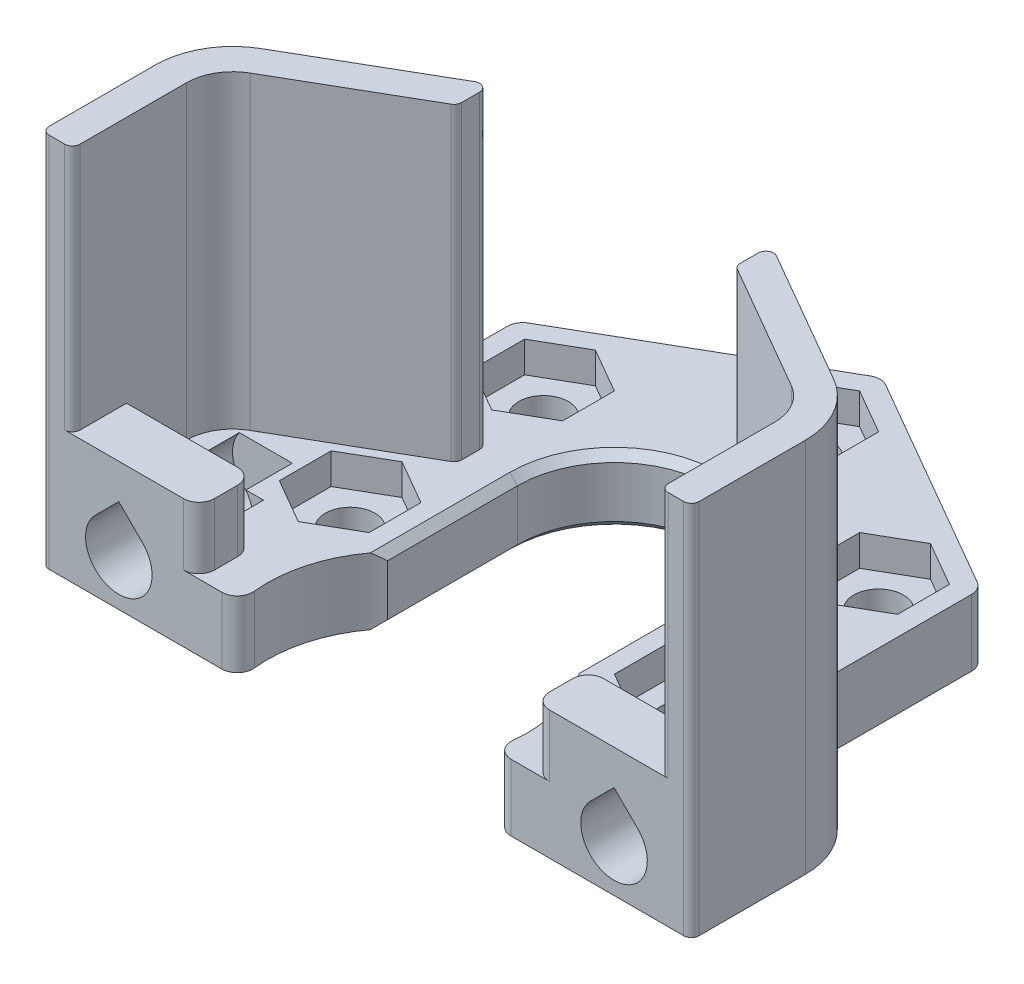
SolidWorks part; units mm, degrees
ref_plane "Front Plane" through (0, 0, 0) normal (0, 0, 1) x (1, 0, 0)
ref_plane "Top Plane" through (0, 0, 0) normal (0, 1, 0) x (1, 0, 0)
ref_plane "Right Plane" through (0, 0, 0) normal (1, 0, 0) x (0, 0, -1)
sketch "Sketch1" plane through (0, 0, 0) normal (0, 1, 0) x (1, 0, 0)
  line L0 (0, 0) -> (0, -54.0828) construction
  line L1 (0, 17.3205) -> (-15, 8.6603)
  line L2 (-15, 8.6603) -> (-15, -8.6603)
  line L3 (-15, -8.6603) -> (-6.25, -13.7121)
  line L4 (6.25, -13.7121) -> (15, -8.6603)
  line L5 (15, -8.6603) -> (15, 8.6603)
  line L6 (15, 8.6603) -> (0, 17.3205)
  line L7 (0, -54.6431) -> (0, 54.6431) construction
  line L8 (6.25, 0) -> (6.25, -13.7121)
  line L9 (-6.25, 0) -> (-6.25, -13.7121)
  line L11 (0, 12.5) -> (-10.8253, 6.25) construction
  line L12 (-10.8253, 6.25) -> (-10.8253, -6.25) construction
  line L13 (-10.8253, -6.25) -> (0, -12.5) construction
  line L14 (0, -12.5) -> (10.8253, -6.25) construction
  line L15 (10.8253, -6.25) -> (10.8253, 6.25) construction
  line L16 (10.8253, 6.25) -> (0, 12.5) construction
  circle A0 centre (0, 0) radius 15 construction
  arc A1 (6.25, 0) -> (-6.25, 0) centre (0, 0) ccw
  circle A2 centre (0, 0) radius 10.8253 construction
  circle A3 centre (0, 12.5) radius 1.6
  circle A4 centre (10.8253, 6.25) radius 1.6
  circle A5 centre (10.8253, -6.25) radius 1.6
  circle A6 centre (-10.8253, -6.25) radius 1.6
  circle A7 centre (-10.8253, 6.25) radius 1.6
  point P1 (0, -27.0414)
  dimension "D4" = 3.2
  dimension "D1" = 12.5
  dimension "D2" = 30
  dimension "D3" = 25
extrude "Boss-Extrude1" add sketch "Sketch1" along normal blind 4.3
fillet "Fillet1" radius 1 7 edges at (15, 2.15, -8.6603) (0, 2.15, -17.3205) (-15, 2.15, -8.6603) (-6.25, 2.15, 13.7121) (6.25, 2.15, 13.7121) (15, 2.15, 8.6603) (-15, 2.15, 8.6603)
sketch "Sketch2" plane through (0, 4.3, 0) normal (0, 1, 0) x (1, 0, 0)
  line L1 (0, 15.8486) -> (-2.9, 14.1743)
  line L2 (-2.9, 14.1743) -> (-2.9, 10.8257)
  line L3 (-2.9, 10.8257) -> (0, 9.1514)
  line L4 (0, 9.1514) -> (2.9, 10.8257)
  line L5 (2.9, 10.8257) -> (2.9, 14.1743)
  line L6 (2.9, 14.1743) -> (0, 15.8486)
  line L7 (13.7253, 4.5757) -> (13.7253, 7.9243)
  line L8 (13.7253, 7.9243) -> (10.8253, 9.5986)
  line L9 (10.8253, 9.5986) -> (7.9253, 7.9243)
  line L10 (7.9253, 7.9243) -> (7.9253, 4.5757)
  line L11 (7.9253, 4.5757) -> (10.8253, 2.9014)
  line L12 (10.8253, 2.9014) -> (13.7253, 4.5757)
  line L13 (13.7253, -4.5757) -> (10.8253, -2.9014)
  line L14 (10.8253, -2.9014) -> (7.9253, -4.5757)
  line L15 (7.9253, -4.5757) -> (7.9253, -7.9243)
  line L16 (7.9253, -7.9243) -> (10.8253, -9.5986)
  line L17 (10.8253, -9.5986) -> (13.7253, -7.9243)
  line L18 (13.7253, -7.9243) -> (13.7253, -4.5757)
  line L19 (-13.7253, -4.5757) -> (-13.7253, -7.9243)
  line L20 (-13.7253, -7.9243) -> (-10.8253, -9.5986)
  line L21 (-10.8253, -9.5986) -> (-7.9253, -7.9243)
  line L22 (-7.9253, -7.9243) -> (-7.9253, -4.5757)
  line L23 (-7.9253, -4.5757) -> (-10.8253, -2.9014)
  line L24 (-10.8253, -2.9014) -> (-13.7253, -4.5757)
  line L25 (-13.7253, 7.9243) -> (-13.7253, 4.5757)
  line L26 (-13.7253, 4.5757) -> (-10.8253, 2.9014)
  line L27 (-10.8253, 2.9014) -> (-7.9253, 4.5757)
  line L28 (-7.9253, 4.5757) -> (-7.9253, 7.9243)
  line L29 (-7.9253, 7.9243) -> (-10.8253, 9.5986)
  line L30 (-10.8253, 9.5986) -> (-13.7253, 7.9243)
  circle A0 centre (0, 12.5) radius 2.9 construction
  circle A1 centre (10.8253, 6.25) radius 2.9 construction
  circle A2 centre (10.8253, -6.25) radius 2.9 construction
  circle A3 centre (-10.8253, -6.25) radius 2.9 construction
  circle A4 centre (-10.8253, 6.25) radius 2.9 construction
  dimension "D1" = 5.8
extrude "Cut-Extrude1" cut sketch "Sketch2" against normal blind 2
sketch "Sketch3" plane through (0, 4.3, 0) normal (0, 1, 0) x (1, 0, 0)
  line L0 (0, 0) -> (0, -38.427) construction
  line L1 (-15, -8.0829) -> (-6.25, -11.98)
  line L2 (-20, -10.9697) -> (-20, -22.3767)
  line L3 (-18.3541, -24.0226) -> (18.3541, -24.0226)
  line L4 (20, -10.9697) -> (20, -22.3767)
  line L5 (0, -54.6431) -> (0, 54.6431) construction
  line L6 (15, -8.0829) -> (20, -10.9697)
  line L7 (-15, -8.0829) -> (-20, -10.9697)
  line L8 (-6.25, -11.98) -> (6.25, -11.98)
  line L9 (6.25, -11.98) -> (15, -8.0829)
  line L10 (-0.5, 17.0318) -> (-14.5, 8.9489) construction
  line L11 (14.5, 8.9489) -> (0.5, 17.0318) construction
  circle A0 centre (0, -14.0226) radius 10 construction
  arc A3 (20, -22.3767) -> (18.3541, -24.0226) centre (18.3541, -22.3767) cw
  arc A4 (-20, -22.3767) -> (-18.3541, -24.0226) centre (-18.3541, -22.3767) ccw
  point P31 (20, -24.0226)
  point P34 (-20, -24.0226)
  dimension "D1" = 20
  dimension "D2" = 40
extrude "Boss-Extrude2" add sketch "Sketch3" against normal up to surface (4.3 mm away) up to face at (-10.8253, 0, 7.85)
sketch "Sketch4" plane through (0, 4.3, 0) normal (0, 1, 0) x (1, 0, 0)
  line L0 (0, -54.6431) -> (0, 54.6431) construction
  circle A0 centre (0, -14.0226) radius 10 construction
  circle A1 centre (0, -14.0226) radius 8.4
  dimension "D1" = 20
  dimension "D2" = 16.8
extrude "Cut-Extrude2" cut sketch "Sketch4" against normal through all
sketch "Sketch5" plane through (0, 4.3, 0) normal (0, 1, 0) x (1, 0, 0)
  line L0 (-20, -10.9697) -> (-20, -22.3767) construction
  line L1 (-20, -16.0226) -> (20, -16.0226)
  line L2 (-20, -16.0226) -> (-20, -24.0226)
  line L3 (-20, -24.0226) -> (20, -24.0226)
  line L4 (20, -16.0226) -> (20, -24.0226)
  line L5 (-18.3541, -24.0226) -> (18.3541, -24.0226) construction
  line L6 (20, -22.3767) -> (20, -10.9697) construction
  point P0 (0, -16.0226)
  dimension "D1" = 8
extrude "Cut-Extrude3" cut sketch "Sketch5" against normal through all
other "Move Face1" face at (17.5, 2.15, 9.5263) face at (-17.5, 2.15, 9.5263) offset 5 parameters "D1"=5
sketch "Sketch6" plane through (0, 4.3, 0) normal (0, 1, 0) x (1, 0, 0)
  line L0 (-20, -12.5226) -> (-8.265, -12.5226)
  line L1 (8.265, -12.5226) -> (20, -12.5226)
  line L12 (8.1584, -16.0226) -> (20, -16.0226)
  line L13 (20, -16.0226) -> (20, -5.1962)
  line L14 (20, -5.1962) -> (15, -2.3094)
  line L15 (15, -2.3094) -> (15, 8.0829)
  line L16 (14.5, 8.9489) -> (0.5, 17.0318)
  line L17 (-0.5, 17.0318) -> (-14.5, 8.9489)
  line L18 (-15, 8.0829) -> (-15, -2.3094)
  line L19 (-15, -2.3094) -> (-20, -5.1962)
  line L20 (-20, -5.1962) -> (-20, -16.0226)
  line L21 (-20, -16.0226) -> (-8.1584, -16.0226)
  line L22 (-6.25, -8.4104) -> (-6.25, 0)
  line L23 (6.25, 0) -> (6.25, -8.4104)
  line L24 (8.1584, -16.0226) -> (20, -16.0226)
  line L25 (20, -16.0226) -> (20, -12.5226)
  line L32 (-20, -12.5226) -> (-20, -16.0226)
  line L33 (-20, -16.0226) -> (-8.1584, -16.0226)
  arc A6 (15, 8.0829) -> (14.5, 8.9489) centre (14, 8.0829) ccw
  arc A7 (0.5, 17.0318) -> (-0.5, 17.0318) centre (0, 16.1658) ccw
  arc A8 (-14.5, 8.9489) -> (-15, 8.0829) centre (-14, 8.0829) ccw
  arc A9 (-6.25, -8.4104) -> (-8.1584, -16.0226) centre (0, -14.0226) ccw
  arc A10 (6.25, 0) -> (-6.25, 0) centre (0, 0) ccw
  arc A11 (8.1584, -16.0226) -> (6.25, -8.4104) centre (0, -14.0226) ccw
  arc A15 (-8.265, -12.5226) -> (-8.1584, -16.0226) centre (0, -14.0226) ccw
  arc A17 (8.1584, -16.0226) -> (8.265, -12.5226) centre (0, -14.0226) ccw
  dimension "D2" = 3.5
  dimension "D1" = 0
extrude "Boss-Extrude3" add sketch "Sketch6" along normal blind 4
sketch "Sketch7" plane through (0, 0, 16.0226) normal (0, 0, 1) x (1, 0, 0)
  circle A0 centre (-16, 3) radius 2.15 construction
  circle A1 centre (-16, 3) radius 2.15
  circle A2 centre (16, 3) radius 2.15 construction
  circle A3 centre (16, 3) radius 2.15
extrude "Cut-Extrude4" cut sketch "Sketch7" against normal up to surface (3.5 mm away) up to face at (-14.1325, 6.3, 12.5226)
sketch "Sketch8" plane through (0, 0, 12.5226) normal (0, 0, -1) x (-1, 0, 0)
  line L0 (0, 0) -> (0, 29.9924) construction
  line L1 (16, 6.2909) -> (13.15, 4.6454)
  line L2 (13.15, 4.6454) -> (13.15, 1.3546)
  line L3 (13.15, 1.3546) -> (16, -0.2909)
  line L4 (16, -0.2909) -> (18.85, 1.3546)
  line L5 (18.85, 1.3546) -> (18.85, 4.6454)
  line L6 (18.85, 4.6454) -> (16, 6.2909)
  line L7 (0, 54.6431) -> (0, -54.6431) construction
  line L8 (-18.85, 4.6454) -> (-16, 6.2909)
  line L9 (-18.85, 1.3546) -> (-18.85, 4.6454)
  line L10 (-16, -0.2909) -> (-18.85, 1.3546)
  line L11 (-13.15, 1.3546) -> (-16, -0.2909)
  line L12 (-13.15, 4.6454) -> (-13.15, 1.3546)
  line L13 (-16, 6.2909) -> (-13.15, 4.6454)
  circle A0 centre (16, 3) radius 2.85 construction
  arc A1 (17.7125, 4.3) -> (14.2875, 4.3) centre (16, 3) ccw construction
  circle A2 centre (-16, 3) radius 2.85 construction
  dimension "D1" = 5.7
extrude "Cut-Extrude5" cut sketch "Sketch8" along normal blind 3
sketch "Sketch9" plane through (0, 4.3, 0) normal (0, 1, 0) x (1, 0, 0)
  line L0 (-8.265, -12.5226) -> (-13.15, -12.5226) construction
  line L1 (-10.8253, -12.5226) -> (10.8253, -12.5226)
  line L2 (-10.8253, -12.5226) -> (-10.8253, -16.0226)
  line L3 (-10.8253, -16.0226) -> (10.8253, -16.0226)
  line L4 (10.8253, -12.5226) -> (10.8253, -16.0226)
  line L5 (8.1584, -16.0226) -> (20, -16.0226) construction
extrude "Cut-Extrude6" cut sketch "Sketch9" along normal up to surface (4 mm away) up to face at (-14.152, 8.3, 14.274)
fillet "Fillet2" radius 1 12 edges at (15, 2.15, 2.3094) (20, 2.15, 5.1962) (20, 6.3, 12.5226) (-8.1584, 2.15, 16.0226) (8.1584, 2.15, 16.0226) (10.8253, 6.3, 16.0226) (10.8253, 6.3, 12.5226) (-10.8253, 6.3, 16.0226) (-10.8253, 6.3, 12.5226) (-20, 6.3, 12.5226) (-20, 2.15, 5.1962) (-15, 2.15, 2.3094)
chamfer "Chamfer1" distance 0.5 angle 45 6 edges at (-6.25, 4.3, 4.2052) (0, 4.3, -6.25) (6.25, 4.3, 4.2052) (6.25, 0, 4.2052) (0, 0, -6.25) (-6.25, 0, 4.2052)
sketch "Sketch10" plane through (0, 0, 16.0226) normal (0, 0, 1) x (1, 0, 0)
  line L0 (-17.5203, 4.5203) -> (-16, 6.0406)
  line L2 (-16, 6.0406) -> (-14.4797, 4.5203)
  line L3 (14.4797, 4.5203) -> (16, 6.0406)
  line L4 (16, 6.0406) -> (17.5203, 4.5203)
  circle A0 centre (-16, 3) radius 2.15 construction
  circle A1 centre (16, 3) radius 2.15 construction
  arc A2 (14.4797, 4.5203) -> (17.5203, 4.5203) centre (16, 3) ccw
  arc A3 (-17.5203, 4.5203) -> (-14.4797, 4.5203) centre (-16, 3) ccw
extrude "Cut-Extrude7" cut sketch "Sketch10" against normal up to surface (3.5 mm away) up to face at (18.15, 3, 12.5226)
sketch "Sketch11" plane through (0, 4.3, 0) normal (0, 1, 0) x (1, 0, 0)
  line L0 (9, -1.1547) -> (19, -6.9282)
  line L1 (19, -6.9282) -> (19, -16.0226)
  line L2 (11.8253, -16.0226) -> (20, -16.0226) construction
  line L3 (19, -16.0226) -> (21, -16.0226)
  line L4 (21, -16.0226) -> (21, -5.7735)
  line L5 (21, -5.7735) -> (9, 1.1547)
  line L6 (9, 1.1547) -> (9, -1.1547)
  line L7 (19.5, -4.9075) -> (15.5, -2.5981) construction
  line L8 (15, -1.7321) -> (15, 8.0829) construction
  line L9 (0, 0) -> (0, -19.4821) construction
  line L10 (0, -54.6431) -> (0, 54.6431) construction
  line L11 (-9, 1.1547) -> (-9, -1.1547)
  line L12 (-21, -5.7735) -> (-9, 1.1547)
  line L13 (-21, -16.0226) -> (-21, -5.7735)
  line L14 (-19, -16.0226) -> (-21, -16.0226)
  line L15 (-19, -6.9282) -> (-19, -16.0226)
  line L16 (-9, -1.1547) -> (-19, -6.9282)
  dimension "D1" = 2
  dimension "D2" = 6
  dimension "D3" = 2
extrude "Boss-Extrude4" add sketch "Sketch11" against normal up to surface (4.3 mm away) and the other way blind 20 up to face at (-10.8253, 0, -4.65)
fillet "Fillet3" radius 3 2 edges at (19, 14.3, 6.9282) (-19, 14.3, 6.9282)
fillet "Fillet4" radius 5 2 edges at (21, 12.15, 5.7735) (-21, 12.15, 5.7735)
fillet "Fillet5" radius 0.5 8 edges at (-9, 14.3, -1.1547) (-9, 14.3, 1.1547) (9, 14.3, -1.1547) (9, 14.3, 1.1547) (21, 12.15, 16.0226) (19, 16.3, 16.0226) (-19, 16.3, 16.0226) (-21, 12.15, 16.0226)
sketch "Sketch12" plane through (0, 0, 16.0226) normal (0, 0, 1) x (1, 0, 0)
  line L0 (-16, 6.0406) -> (-17.5203, 4.5203) construction
  line L1 (-14.4797, 4.5203) -> (-16, 6.0406) construction
  line L2 (-16, 6.0406) -> (-17.5203, 4.5203)
  line L3 (-14.4797, 4.5203) -> (-16, 6.0406)
  line L4 (16, 6.0406) -> (14.4797, 4.5203) construction
  line L5 (17.5203, 4.5203) -> (16, 6.0406) construction
  line L6 (16, 6.0406) -> (14.4797, 4.5203)
  line L7 (17.5203, 4.5203) -> (16, 6.0406)
  arc A0 (-17.5203, 4.5203) -> (-14.4797, 4.5203) centre (-16, 3) ccw construction
  arc A1 (-17.5203, 4.5203) -> (-14.4797, 4.5203) centre (-16, 3) ccw
  arc A2 (14.4797, 4.5203) -> (17.5203, 4.5203) centre (16, 3) ccw construction
  arc A3 (14.4797, 4.5203) -> (17.5203, 4.5203) centre (16, 3) ccw
extrude "Cut-Extrude8" cut sketch "Sketch12" against normal offset from surface (9.5 mm away) 3 up to face at (-16, 1.8849, 9.5226) offset beyond the face yes
